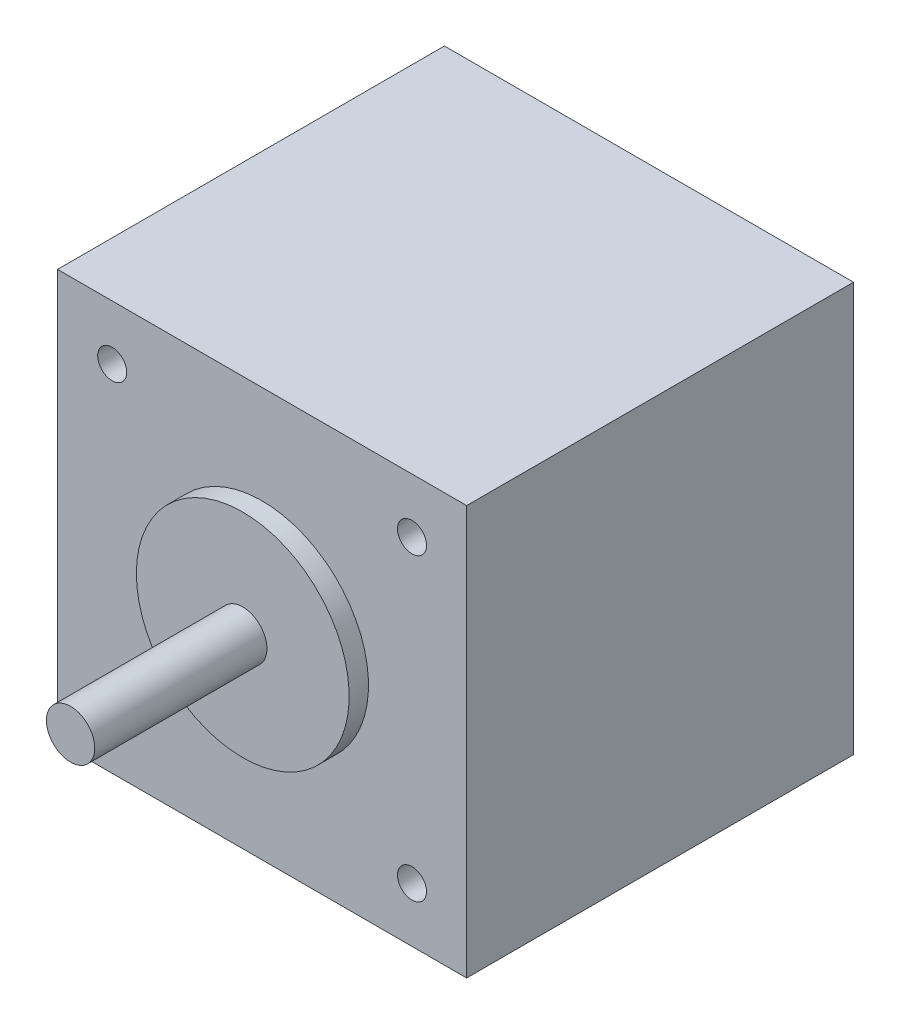
SolidWorks part; units mm, degrees
ref_plane "Спереди" through (0, 0, 0) normal (0, 0, 1) x (1, 0, 0)
ref_plane "Сверху" through (0, 0, 0) normal (0, 1, 0) x (1, 0, 0)
ref_plane "Справа" through (0, 0, 0) normal (1, 0, 0) x (0, 0, -1)
other "Configuration Table"
sketch "Эскиз1" plane through (0, 0, 0) normal (0, 0, 1) x (1, 0, 0)
  line L1 (-21.15, -21.15) -> (21.15, -21.15)
  line L2 (-21.15, -21.15) -> (-21.15, 21.15)
  line L3 (-21.15, 21.15) -> (21.15, 21.15)
  line L4 (21.15, -21.15) -> (21.15, 21.15)
  line L5 (-21.15, -21.15) -> (21.15, 21.15) construction
  line L6 (-21.15, 21.15) -> (21.15, -21.15) construction
  point P0 (0, 0)
  dimension "D1" = 42.3
  dimension "D2" = 42.3
extrude "Корпус" add sketch "Эскиз1" along normal blind 40
sketch "Эскиз2" plane through (0, 0, 0) normal (0, 0, 1) x (1, 0, 0)
  circle A0 centre (0, 0) radius 2.5
extrude "Вал_ПРЕДВ" add sketch "Эскиз2" along normal blind 59.8
sketch "Эскиз3" plane through (0, 0, 0) normal (0, 0, 1) x (1, 0, 0)
  circle A0 centre (0, 0) radius 11
  dimension "D1" = 22
extrude "Буртик_ПРЕДВ" add sketch "Эскиз3" along normal blind 42
sketch "Эскиз4" plane through (0, 0, 0) normal (0, 0, 1) x (1, 0, 0)
  circle A0 centre (0, 0) radius 8
  dimension "D1" = 16
sketch "Эскиз5" plane through (0, 0, 0) normal (0, 0, 1) x (1, 0, 0)
  circle A0 centre (-15.5, -15.5) radius 1.5
  circle A1 centre (-15.5, 15.5) radius 1.5
  circle A2 centre (15.5, -15.5) radius 1.5
  circle A3 centre (15.5, 15.5) radius 1.5
  dimension "D1" = 3
  dimension "D2" = 3
  dimension "D3" = 3
  dimension "D4" = 3
extrude "Крепеж_М3_ПРЕДВ" cut sketch "Эскиз5" against normal blind 4.5 from offset 40
equation "\"Мотор X ширина корпуса\"= 42.3"
equation "\"Мотор X высота корпуса\"= 42.3"
equation "\"Мотор X длина корпуса\"= 40"
equation "\"Мотор X вылет вала\"= 19.8"
equation "\"Мотор Y ширина корпуса\"= 42.3"
equation "\"Мотор Y высота корпуса\"= 42.3"
equation "\"Мотор Y длина корпуса\"= 48"
equation "\"Мотор Y вылет вала\"= 30"
equation "\"Мотор Z ширина корпуса\"= 42"
equation "\"Мотор Z высота корпуса\"= 42"
equation "\"Мотор Z длина корпуса\"= 40"
equation "\"Мотор Z вылет вала\"= 23"
equation "\"Мотор диаметр вала ПРЕДВ\"= 5"
equation "\"Мотор шаг крепления ПРЕДВ\"= 31"
equation "\"Мотор диаметр отверстий ПРЕДВ\"= 3"
equation "\"Мотор глубина отверстий ПРЕДВ\"= 4.5"
equation "\"Мотор диаметр буртика ПРЕДВ\"= 22"
equation "\"Мотор высота буртика ПРЕДВ\"= 2"
equation "\"Мотор диаметр шкива ПРЕДВ\"= 16"
equation "\"Мотор длина шкива ПРЕДВ\"= 12"
equation "\"Мотор отступ шкива ПРЕДВ\"= 5"
equation "\"Мотор X шаг градусов\"= 1.8"
equation "\"Мотор Y шаг градусов\"= 1.8"
equation "\"Мотор Z шаг градусов\"= 1.8"
equation "\"Мотор Y диаметр ротора\"= 25.78"
equation "\"D1@Эскиз1\" = \"Мотор X ширина корпуса\""
equation "\"D1@Корпус\" = \"Мотор X длина корпуса\""
equation "\"D1@Эскиз2\" = \"Мотор диаметр вала ПРЕДВ\""
equation "\"D1@Вал_ПРЕДВ\" = \"Мотор X длина корпуса\" + \"Мотор X вылет вала\""
equation "\"D1@Эскиз3\" = \"Мотор диаметр буртика ПРЕДВ\""
equation "\"D1@Буртик_ПРЕДВ\" = \"Мотор X длина корпуса\" + \"Мотор высота буртика ПРЕДВ\""
equation "\"D1@Эскиз4\" = \"Мотор диаметр шкива ПРЕДВ\""
equation "\"D1@Эскиз5\" = \"Мотор диаметр отверстий ПРЕДВ\""
equation "\"D2@Эскиз5\" = \"Мотор диаметр отверстий ПРЕДВ\""
equation "\"D3@Эскиз5\" = \"Мотор диаметр отверстий ПРЕДВ\""
equation "\"D4@Эскиз5\" = \"Мотор диаметр отверстий ПРЕДВ\""
equation "\"D1@Крепеж_М3_ПРЕДВ\" = \"Мотор глубина отверстий ПРЕДВ\""
equation "\"D19@Крепеж_М3_ПРЕДВ\" = \"Мотор X длина корпуса\""
equation "\"Ширина груза\"= 420"
equation "\"Глубина груза\"= 490"
equation "\"Высота груза\"= 297"
equation "\"Ширина ячейки\"= \"Ширина груза\" + 10"
equation "\"Глубина ячейки\"= \"Глубина груза\" + 10"
equation "\"Высота ячейки\"= \"Высота груза\" + 10 + 13"
equation "\"Колво ячеек ширина\"= 2"
equation "\"Колво ячеек высота\"= 2"
equation "\"Толщина стенки\" = 6"
equation "\"Крепление дверцы\"= 5 "
equation "\"Ширина рейки\"= \"Толщина шестерни\""
equation "\"Высота рейки\"= 20"
equation "\"Высота пола\"= \"Толщина стенки\" * 2"
equation "\"Колво полозьев\"= 5"
equation "\"Отступ рейки\"= 20"
equation "\"Глубина каретки\"= \"Глубина ячейки\" + 30 + \"Мотор Y высота корпуса\" + 20"
equation "\"Отступ шпильки\"= 26"
equation "\"Диаметр шпильки\"= 5"
equation "\"Длинна шпильки\"= ( \"Высота ячейки\" + \"Толщина стенки\" + \"Высота пола\" ) * \"Колво ячеек высота\" + ( \"Толщина стенки\" + \"Отступ рейки\" ) * 2 "
equation "\"Ширина пластины\"= 50  "
equation "\"Высота зона выгрузки\"= \"Высота ячейки\" * 2 + \"Толщина стенки\" * 2"
equation "\"Колво выгрузки\"= 1"
equation "\"Отступ крепления мотора фиксации\" = 30"
equation "\"Диаметр оси\"= 10"
equation "\"Диаметр ролика\"= 20"
equation "\"Колво роликов\"= 10"
equation "\"Шаг роликов\"= \"Диаметр ролика\" + 20"
equation "\"Ширина ячейки выгрузки\"= \"Ширина ячейки\" + \"Толщина стенки\" + \"Отступ крепления мотора фиксации\"*2"
equation "\"Длинна рейки\"= ( \"Ширина ячейки\" + \"Толщина стенки\" + \"Крепление дверцы\" ) * \"Колво ячеек ширина\" + \"Ширина ячейки выгрузки\" * \"Колво выгрузки\" + \"Толщина стенки\""
equation "\"Толщина шестерни\"= 10"
